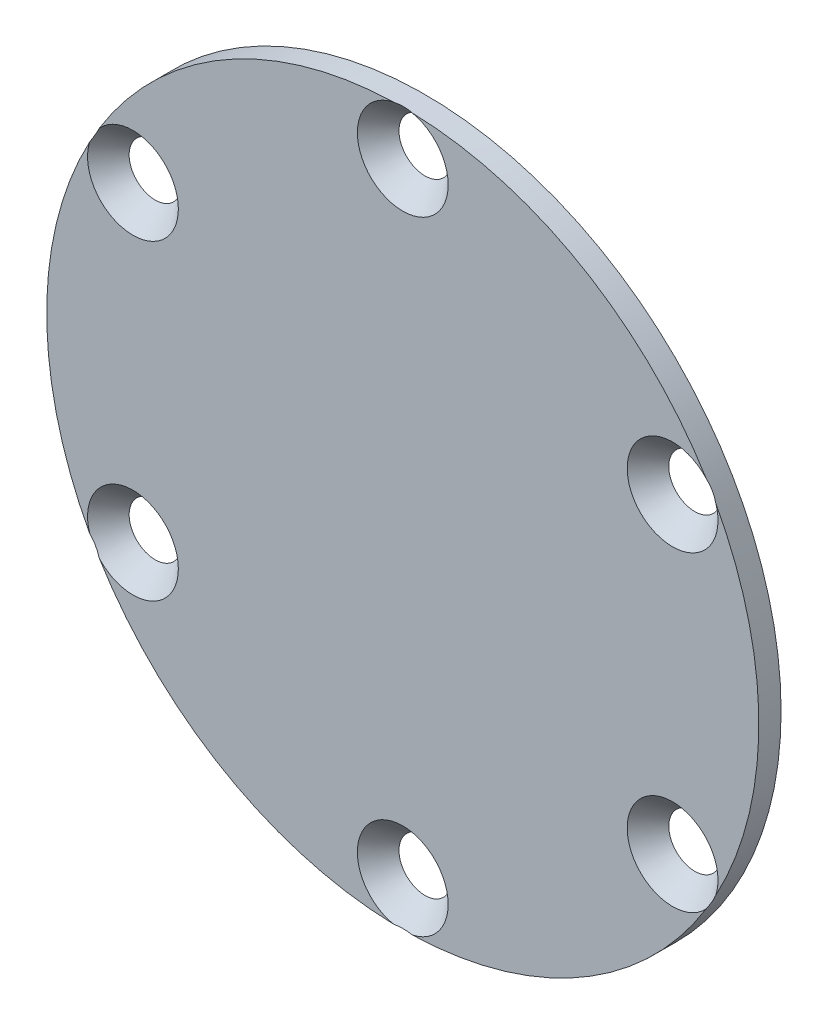
SolidWorks part; units mm, degrees
material "6061-T6 (SS)"
ref_plane "Front Plane" through (0, 0, 0) normal (0, 0, 1) x (1, 0, 0)
ref_plane "Top Plane" through (0, 0, 0) normal (0, 1, 0) x (1, 0, 0)
ref_plane "Right Plane" through (0, 0, 0) normal (1, 0, 0) x (0, 0, -1)
sketch "Sketch1" plane through (0, 0, 0) normal (0, 0, 1) x (1, 0, 0)
  circle A0 centre (0, 0) radius 25.4
  dimension "D1" = 50.8
extrude "Boss-Extrude1" add sketch "Sketch1" along normal blind 1.5875
sketch "Sketch2" plane through (0, 0, 1.5875) normal (0, 0, 1) x (1, 0, 0)
  circle A0 centre (0, 0) radius 22.225 construction
  circle A1 centre (0, 0) radius 25.4 construction
  dimension "D1" = 3.175
hole_wizard "CSK for #4 Flat Head Socket Cap Screw1" positions "Sketch4" profile "Sketch3" countersink size "#4" standard "Ansi Inch" end condition through all
sketch "Sketch4" plane through (0, 0, 1.5875) normal (0, 0, 1) x (1, 0, 0)
  circle A0 centre (0, 0) radius 22.225 construction
  point P0 (0, 22.225)
  point P16 (19.2474, 11.1125)
  point P17 (19.2474, -11.1125)
  point P18 (0, -22.225)
  point P19 (-19.2474, -11.1125)
  point P20 (-19.2474, 11.1125)
  dimension "D1" = 6
sketch "Sketch3" plane through (0, 22.225, 1.5875) normal (1, 0, 0) x (0, -1, 0)
  line L0 (0, 0) -> (0, 1.5875)
  line L1 (0, 1.5875) -> (1.632, 1.5875)
  line L2 (1.632, 1.5875) -> (1.632, 1.8481)
  line L3 (1.632, 1.8481) -> (3.2385, 0)
  line L5 (3.2385, 0) -> (0, 0)
  line L6 (-1.632, 1.8481) -> (-3.2385, 0) construction
  line L11 (0, -6.35) -> (0, 107.95) construction
  dimension "Thru Hole Dia." = 3.2639
  dimension "Thru Hole Depth" = 1.5875
  dimension "Near C'Sink Dia." = 6.477
  dimension "Near C'Sink Angle" = 82
